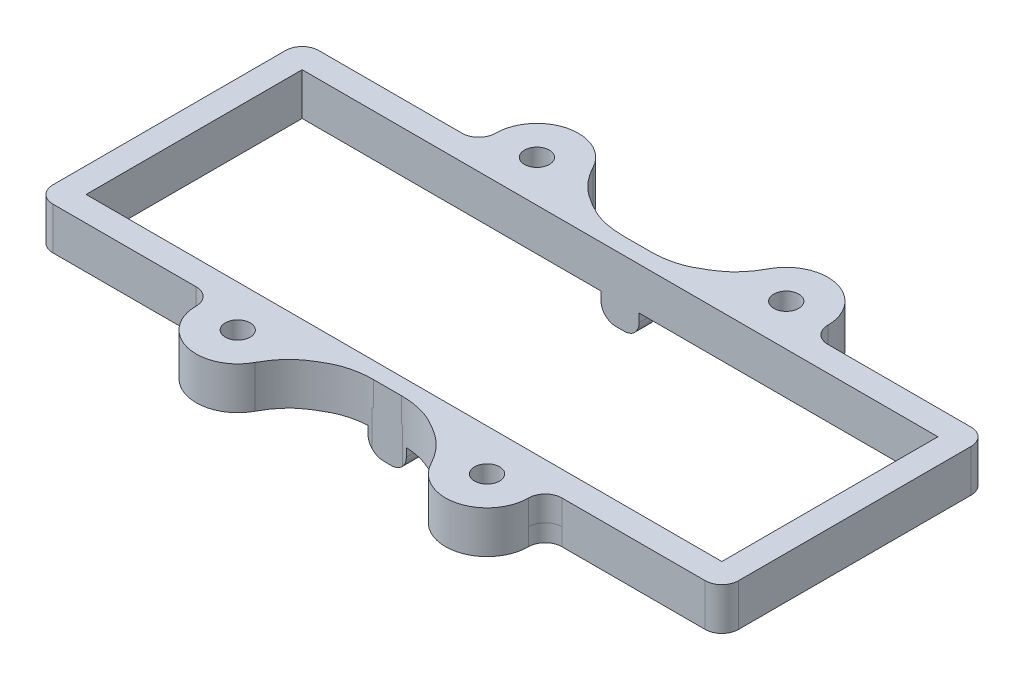
SolidWorks part; units mm, degrees
ref_plane "Front Plane" through (0, 0, 0) normal (0, 0, 1) x (1, 0, 0)
ref_plane "Top Plane" through (0, 0, 0) normal (0, 1, 0) x (1, 0, 0)
ref_plane "Right Plane" through (0, 0, 0) normal (1, 0, 0) x (0, 0, -1)
sketch "Sketch1" plane through (0, 0, 0) normal (0, 1, 0) x (1, 0, 0)
  line L0 (-44.593, 3.4751) -> (37.907, 3.4751) construction
  line L1 (-44.593, 19.4751) -> (37.907, 19.4751)
  line L2 (-44.593, 19.4751) -> (-44.593, -12.5249)
  line L3 (-44.593, -12.5249) -> (37.907, -12.5249)
  line L4 (37.907, 19.4751) -> (37.907, -12.5249)
  line L5 (-41.593, 16.4751) -> (34.907, 16.4751)
  line L6 (-41.593, 16.4751) -> (-41.593, -9.5249)
  line L7 (-41.593, -9.5249) -> (34.907, -9.5249)
  line L8 (34.907, 16.4751) -> (34.907, -9.5249)
  line L9 (-3.343, 19.4751) -> (-3.343, -12.5249) construction
  line L10 (16.657, -12.5249) -> (16.657, -19.5249)
  line L11 (-23.343, 19.4751) -> (16.657, 19.4751)
  line L12 (-23.343, 19.4751) -> (-23.343, 26.4751)
  line L13 (-23.343, 26.4751) -> (16.657, 26.4751)
  line L14 (16.657, 19.4751) -> (16.657, 26.4751)
  line L15 (-23.343, -19.5249) -> (16.657, -19.5249)
  line L16 (-23.343, -12.5249) -> (-23.343, -19.5249)
  line L17 (-23.343, -12.5249) -> (16.657, -12.5249)
  line L18 (-25.2775, 21.4751) -> (22.0201, 21.4751) construction
  circle A0 centre (-18.343, 21.4751) radius 1.5
  circle A1 centre (11.657, 21.4751) radius 1.5
  circle A2 centre (11.657, -14.5249) radius 1.5
  circle A3 centre (-18.343, -14.5249) radius 1.5
  dimension "D1" = 82.5
  dimension "D2" = 32
  dimension "D3" = 76.5
  dimension "D4" = 26
  dimension "D5" = 13
  dimension "D6" = 38.25
  dimension "D7" = 40
  dimension "D8" = 20
  dimension "D9" = 7
  dimension "D10" = 30
  dimension "D12" = 15
  dimension "D13" = 2
extrude "Boss-Extrude1" add sketch "Sketch1" along normal blind 2.085 contours L3 L16 L15 L10 A2 A3 | L4 L1 L2 L3 L5 L8 L7 L6 | L1 L14 L13 L12 A1 A0
sketch "Sketch2" plane through (0, 0, 0) normal (0, -1, 0) x (1, 0, 0)
  line L0 (-3.343, 19.5249) -> (-3.343, -26.4751) construction
  line L1 (-23.343, 19.5249) -> (16.657, 19.5249) construction
  line L2 (-23.343, -26.4751) -> (16.657, -26.4751) construction
  line L3 (-41.593, -3.4751) -> (34.907, -3.4751) construction
  line L4 (-5.843, 19.5249) -> (-0.843, 19.5249)
  line L5 (-5.843, 19.5249) -> (-5.843, 9.5249)
  line L6 (-5.843, 9.5249) -> (-0.843, 9.5249)
  line L7 (-0.843, 19.5249) -> (-0.843, 9.5249)
  line L8 (-41.593, -16.4751) -> (-41.593, 9.5249) construction
  line L9 (34.907, -16.4751) -> (34.907, 9.5249) construction
  line L10 (-0.843, -26.4751) -> (-0.843, -16.4751)
  line L11 (-5.843, -16.4751) -> (-0.843, -16.4751)
  line L12 (-5.843, -26.4751) -> (-5.843, -16.4751)
  line L13 (-5.843, -26.4751) -> (-0.843, -26.4751)
  dimension "D1" = 5
  dimension "D2" = 10
  dimension "D3" = 2.5
extrude "Boss-Extrude2" add sketch "Sketch2" along normal blind 3
fillet "Fillet1" radius 2 4 edges at (-5.843, -3, 14.5249) (-0.843, -3, 14.5249) (-0.843, -3, -21.4751) (-5.843, -3, -21.4751)
fillet "Fillet2" radius 2 4 edges at (-44.593, 1.0425, 12.5249) (-44.593, 1.0425, -19.4751) (37.907, 1.0425, -19.4751) (37.907, 1.0425, 12.5249)
sketch "Sketch3" plane through (0, 0, -26.4751) normal (0, 0, -1) x (-1, 0, 0)
  line L8 (23.343, 0) -> (5.843, 0) construction
  line L9 (6.1655, 0) -> (0.1244, 0)
  line L10 (6.1655, 0) -> (6.1655, -3.3793)
  line L11 (6.1655, -3.3793) -> (0.1244, -3.3793)
  line L12 (0.1244, 0) -> (0.1244, -3.3793)
  line L16 (2.843, -2.8) -> (3.843, -2.8)
  line L17 (5.643, 0.2) -> (23.143, 0.2)
  line L18 (23.143, 0.2) -> (23.143, 1.885)
  line L19 (23.143, 1.885) -> (-16.457, 1.885)
  line L20 (-16.457, 1.885) -> (-16.457, 0.2)
  line L21 (-16.457, 0.2) -> (1.043, 0.2)
  line L22 (2.843, -2.8) -> (3.843, -2.8)
  line L23 (5.643, 0.2) -> (23.143, 0.2)
  line L24 (23.143, 0.2) -> (23.143, 1.885)
  line L25 (23.143, 1.885) -> (-16.457, 1.885)
  line L26 (-16.457, 1.885) -> (-16.457, 0.2)
  line L27 (-16.457, 0.2) -> (1.043, 0.2)
  line L28 (1.043, 0.2) -> (1.043, -1)
  line L29 (1.043, 0.2) -> (1.043, -1)
  line L30 (5.643, -1) -> (5.643, 0.2)
  line L31 (5.643, -1) -> (5.643, 0.2)
  arc A4 (1.043, -1) -> (2.843, -2.8) centre (2.843, -1) ccw
  arc A5 (3.843, -2.8) -> (5.643, -1) centre (3.843, -1) ccw
  arc A6 (1.043, -1) -> (2.843, -2.8) centre (2.843, -1) ccw
  arc A7 (3.843, -2.8) -> (5.643, -1) centre (3.843, -1) ccw
  line M11 (0.843, 0) -> (0.843, -1)
  arc M12 (0.843, -1) -> (2.843, -3) centre (2.843, -1) ccw
  line M13 (2.843, -3) -> (3.843, -3)
  arc M14 (3.843, -3) -> (5.843, -1) centre (3.843, -1) ccw
  line M15 (5.843, -1) -> (5.843, 0)
  dimension "D1" = 0.2
extrude "Cut-Extrude1" cut sketch "Sketch3" against normal through all contours A7 L22 A6 L29 L9 L31 M11 M12 M13 M14 M15
sketch "Sketch4" plane through (0, 2.085, 0) normal (0, 1, 0) x (1, 0, 0)
  line L0 (-3.343, 18.4751) -> (7.657, 18.4751)
  line L1 (7.657, 18.4751) -> (-14.343, 18.4751)
  line L2 (-5.0256, 18.4751) -> (-1.6603, 18.4751)
  line L3 (37.907, 3.4751) -> (-44.593, 3.4751) construction
  line L4 (37.907, 17.4751) -> (37.907, -10.5249) construction
  line L5 (-44.593, 17.4751) -> (-44.593, -10.5249) construction
  line L6 (11.657, 26.4751) -> (11.657, 33.2921)
  line L7 (11.657, 33.2921) -> (-18.343, 33.2921)
  line L8 (-18.343, 33.2921) -> (-18.343, 26.4751)
  line L9 (-18.343, -26.342) -> (-18.343, -19.5249)
  line L10 (11.657, -26.342) -> (-18.343, -26.342)
  line L11 (11.657, -19.5249) -> (11.657, -26.342)
  line L12 (-5.0256, -11.5249) -> (-1.6603, -11.5249)
  line L13 (7.657, -11.5249) -> (-14.343, -11.5249)
  line L14 (-3.343, -11.5249) -> (7.657, -11.5249)
  circle A0 centre (-18.343, 21.4751) radius 5
  circle A1 centre (11.657, 21.4751) radius 5
  circle A2 centre (11.657, -14.5249) radius 5
  circle A3 centre (-18.343, -14.5249) radius 5
  spline S0 degree 3 poles (-13.9208, 23.8084) (-13.3837, 22.8069) (-12.2321, 21.2227) (-10.1423, 19.8877) (-8.5768, 19.0482) (-6.9016, 18.5983) (-5.7419, 18.469) (-5.0256, 18.4751) knots 0 0 0 0 0.314938 0.52444 0.679222 0.802825 1 1 1 1
  spline S1 degree 3 poles (7.2349, 23.8084) (6.6978, 22.8069) (5.5462, 21.2227) (3.4564, 19.8877) (1.8909, 19.0482) (0.2157, 18.5983) (-0.944, 18.469) (-1.6603, 18.4751) knots 0 0 0 0 0.314938 0.52444 0.679222 0.802825 1 1 1 1
  spline S2 degree 3 poles (7.2349, -16.8583) (6.6978, -15.8568) (5.5462, -14.2726) (3.4564, -12.9376) (1.8909, -12.0981) (0.2157, -11.6482) (-0.944, -11.5188) (-1.6603, -11.5249) knots 0 0 0 0 0.314938 0.52444 0.679222 0.802825 1 1 1 1
  spline S3 degree 3 poles (-13.9208, -16.8583) (-13.3837, -15.8568) (-12.2321, -14.2726) (-10.1423, -12.9376) (-8.5768, -12.0981) (-6.9016, -11.6482) (-5.7419, -11.5188) (-5.0256, -11.5249) knots 0 0 0 0 0.314938 0.52444 0.679222 0.802825 1 1 1 1
  line M7 (-23.343, -19.5249) -> (16.657, -19.5249)
  line M15 (16.657, 26.4751) -> (-23.343, 26.4751)
extrude "Cut-Extrude2" cut sketch "Sketch4" against normal through all contours S1 A1 A0 S0 L1 L0 M15 | L7 L8 L6 M15 | S3 A3 A2 S2 L14 L13 L12 M7 | L11 L9 L10 M7
fillet "Fillet3" radius 5 4 edges at (16.657, 1.0425, -26.4751) (-23.343, 1.0425, -26.4751) (-23.343, 1.0425, 19.5249) (16.657, 1.0425, 19.5249)
fillet "Fillet4" radius 2 12 edges at (16.657, 2.085, 13.5249) (-23.343, 0, 13.5249) (-23.343, 0, -20.4751) (16.657, 0, -20.4751) (16.657, 0, 13.5249) (16.657, 2.085, -20.4751) (-23.343, 1.0425, 12.5249) (-23.343, 1.0425, -19.4751) (16.657, 1.0425, -19.4751) (16.657, 1.0425, 12.5249) (-23.343, 2.085, -20.4751) (-23.343, 2.085, 13.5249)
sketch "Sketch5" plane through (0, 2.085, 0) normal (0, 1, 0) x (1, 0, 0)
  line L0 (-23.343, 21.4751) -> (-23.343, 16.4751)
  line L1 (-41.593, 3.4751) -> (34.907, 3.4751) construction
  line L2 (-41.593, 16.4751) -> (-41.593, -9.5249) construction
  line L3 (34.907, 16.4751) -> (34.907, -9.5249) construction
  line L4 (-3.343, -9.5249) -> (-3.343, 43.7071) construction
  line L5 (-41.593, 16.4751) -> (34.907, 16.4751) construction
  line L6 (-3.343, 18.4751) -> (7.657, 18.4751)
  line L7 (7.657, 18.4751) -> (-14.343, 18.4751)
  line L8 (-14.343, 18.4751) -> (-14.343, 31.9361)
  line L9 (-3.343, 18.4751) -> (-3.343, 35.8237) construction
  line L10 (-5.0256, 18.4751) -> (-1.6603, 18.4751)
  line L11 (-41.593, -9.5249) -> (34.907, -9.5249) construction
  line L12 (-23.343, 16.4751) -> (16.657, 16.4751)
  line L13 (16.657, 16.4751) -> (16.657, 21.4751)
  line L14 (16.657, -9.5249) -> (16.657, -14.5249)
  line L15 (-23.343, -9.5249) -> (16.657, -9.5249)
  line L16 (-5.0256, -11.5249) -> (-1.6603, -11.5249)
  line L17 (7.657, -11.5249) -> (-14.343, -11.5249)
  line L18 (-3.343, -11.5249) -> (7.657, -11.5249)
  line L19 (-23.343, -14.5249) -> (-23.343, -9.5249)
  line L21 (34.907, -9.5249) -> (-41.593, -9.5249)
  line L22 (34.907, -9.5249) -> (34.907, 16.4751)
  line L23 (34.907, 16.4751) -> (-41.593, 16.4751)
  line L24 (-41.593, -9.5249) -> (-41.593, 16.4751)
  line L25 (35.907, -12.5249) -> (-42.593, -12.5249)
  line L26 (37.907, -10.5249) -> (37.907, 17.4751)
  line L27 (35.907, 19.4751) -> (-42.593, 19.4751)
  line L28 (-44.593, -10.5249) -> (-44.593, 17.4751)
  circle A0 centre (-18.343, 21.4751) radius 5
  circle A1 centre (11.657, 21.4751) radius 5
  circle A2 centre (11.657, -14.5249) radius 5
  circle A3 centre (-18.343, -14.5249) radius 5
  arc A4 (-42.593, -12.5249) -> (-44.593, -10.5249) centre (-42.593, -10.5249) cw
  arc A5 (-42.593, 19.4751) -> (-44.593, 17.4751) centre (-42.593, 17.4751) ccw
  arc A6 (37.907, 17.4751) -> (35.907, 19.4751) centre (35.907, 17.4751) ccw
  arc A7 (35.907, -12.5249) -> (37.907, -10.5249) centre (35.907, -10.5249) ccw
  spline S0 degree 3 poles (-13.9208, 23.8084) (-13.3837, 22.8069) (-12.2321, 21.2227) (-10.1423, 19.8877) (-8.5768, 19.0482) (-6.9016, 18.5983) (-5.7419, 18.469) (-5.0256, 18.4751) knots 0 0 0 0 0.314938 0.52444 0.679222 0.802825 1 1 1 1
  spline S1 degree 3 poles (7.2349, 23.8084) (6.6978, 22.8069) (5.5462, 21.2227) (3.4564, 19.8877) (1.8909, 19.0482) (0.2157, 18.5983) (-0.944, 18.469) (-1.6603, 18.4751) knots 0 0 0 0 0.314938 0.52444 0.679222 0.802825 1 1 1 1
  spline S2 degree 3 poles (7.2349, -16.8583) (6.6978, -15.8568) (5.5462, -14.2726) (3.4564, -12.9376) (1.8909, -12.0981) (0.2157, -11.6482) (-0.944, -11.5188) (-1.6603, -11.5249) knots 0 0 0 0 0.314938 0.52444 0.679222 0.802825 1 1 1 1
  spline S3 degree 3 poles (-13.9208, -16.8583) (-13.3837, -15.8568) (-12.2321, -14.2726) (-10.1423, -12.9376) (-8.5768, -12.0981) (-6.9016, -11.6482) (-5.7419, -11.5188) (-5.0256, -11.5249) knots 0 0 0 0 0.314938 0.52444 0.679222 0.802825 1 1 1 1
  circle M5 centre (-18.343, 21.4751) radius 1.5
  circle M6 centre (11.657, 21.4751) radius 1.5
  line M7 (-41.593, 16.4751) -> (34.907, 16.4751)
  line M8 (34.907, 16.4751) -> (34.907, -9.5249)
  line M9 (34.907, -9.5249) -> (-41.593, -9.5249)
  line M10 (-41.593, -9.5249) -> (-41.593, 16.4751)
  circle M11 centre (-18.343, -14.5249) radius 1.5
  circle M12 centre (11.657, -14.5249) radius 1.5
  line M13 (35.907, 19.4751) -> (18.657, 19.4751)
  arc M15 (16.657, 21.4751) -> (11.657, 26.4751) centre (11.657, 21.4751) ccw
  arc M16 (11.657, 26.4751) -> (7.2349, 23.8084) centre (11.657, 21.4751) ccw
  spline M17 degree 3 poles (7.2349, 23.8084) (6.6978, 22.8069) (5.5462, 21.2227) (3.4564, 19.8877) (1.8909, 19.0482) (0.2157, 18.5983) (-0.944, 18.469) (-1.6603, 18.4751) knots 0 0 0 0 0.314938 0.52444 0.679222 0.802825 1 1 1 1 only from (7.2349, 23.8084) to (-1.5064, 18.4751)
  line M18 (-1.5064, 18.4751) -> (-5.1795, 18.4751)
  spline M19 degree 3 poles (-5.0256, 18.4751) (-5.7419, 18.469) (-6.9016, 18.5983) (-8.5768, 19.0482) (-10.1423, 19.8877) (-12.2321, 21.2227) (-13.3837, 22.8069) (-13.9208, 23.8084) knots 0 0 0 0 0.197175 0.320778 0.47556 0.685062 1 1 1 1 only from (-5.1795, 18.4751) to (-13.9208, 23.8084)
  arc M20 (-13.9208, 23.8084) -> (-18.343, 26.4751) centre (-18.343, 21.4751) ccw
  arc M21 (-18.343, 26.4751) -> (-23.343, 21.4751) centre (-18.343, 21.4751) ccw
  line M23 (-25.343, 19.4751) -> (-42.593, 19.4751)
  arc M24 (-42.593, 19.4751) -> (-44.593, 17.4751) centre (-42.593, 17.4751) ccw
  line M25 (-44.593, 17.4751) -> (-44.593, -10.5249)
  arc M26 (-44.593, -10.5249) -> (-42.593, -12.5249) centre (-42.593, -10.5249) ccw
  line M27 (-42.593, -12.5249) -> (-25.343, -12.5249)
  arc M29 (-23.343, -14.5249) -> (-18.343, -19.5249) centre (-18.343, -14.5249) ccw
  arc M30 (-18.343, -19.5249) -> (-13.9208, -16.8583) centre (-18.343, -14.5249) ccw
  spline M31 degree 3 poles (-13.9208, -16.8583) (-13.3837, -15.8568) (-12.2321, -14.2726) (-10.1423, -12.9376) (-8.5768, -12.0981) (-6.9016, -11.6482) (-5.7419, -11.5188) (-5.0256, -11.5249) knots 0 0 0 0 0.314938 0.52444 0.679222 0.802825 1 1 1 1 only from (-13.9208, -16.8583) to (-5.1795, -11.5249)
  line M32 (-5.1795, -11.5249) -> (-1.5064, -11.5249)
  spline M33 degree 3 poles (-1.6603, -11.5249) (-0.944, -11.5188) (0.2157, -11.6482) (1.8909, -12.0981) (3.4564, -12.9376) (5.5462, -14.2726) (6.6978, -15.8568) (7.2349, -16.8583) knots 0 0 0 0 0.197175 0.320778 0.47556 0.685062 1 1 1 1 only from (-1.5064, -11.5249) to (7.2349, -16.8583)
  arc M34 (7.2349, -16.8583) -> (11.657, -19.5249) centre (11.657, -14.5249) ccw
  arc M35 (11.657, -19.5249) -> (16.657, -14.5249) centre (11.657, -14.5249) ccw
  line M37 (18.657, -12.5249) -> (35.907, -12.5249)
  arc M38 (35.907, -12.5249) -> (37.907, -10.5249) centre (35.907, -10.5249) ccw
  line M39 (37.907, -10.5249) -> (37.907, 17.4751)
  arc M40 (37.907, 17.4751) -> (35.907, 19.4751) centre (35.907, 17.4751) ccw
  dimension "D1" = 2
extrude "Boss-Extrude3" add sketch "Sketch5" along normal blind 3 contours A0 L8 M20 M21 M5 | L6 S1 L7 S0 A0 L12 A1 M18 | A0 L0 M7 | L8 A0 M20 | A0 L7 M19 | A1 L6 M17 | A1 M15 M16 M6 | A1 L13 M7 | L19 A3 M9 | A3 M29 M30 M11 | L17 S3 S2 A2 L15 A3 M32 | L17 A3 M31 | A2 L17 M33 | A2 M34 M35 M12 | A2 L14 M9 | L27 L13 L14 L25 M13 M7 M8 M9 M37 M38 M39 M40 | L0 L27 L25 L19 M23 M24 M25 M26 M27 M9 M10 M7 | A2 L25 | A2 L25 M33 | A3 L25 | L25 A3 M31 | A1 L27 | A1 L27 M17 | A0 L8 L27 | A0 L27 M19 | L8 A0 L27
fillet "Fillet5" radius 2 12 edges at (16.2396, 3.585, 12.5249) (17.4483, 2.085, -19.4751) (16.5516, 2.085, -20.4535) (16.2396, 3.585, -19.4751) (-23.2375, 2.085, -20.4535) (-24.1342, 2.085, -19.4751) (-22.9255, 3.585, -19.4751) (-24.1342, 2.085, 12.5249) (-22.9255, 3.585, 12.5249) (-23.2375, 2.085, 13.5034) (17.4483, 2.085, 12.5249) (16.5516, 2.085, 13.5034)
